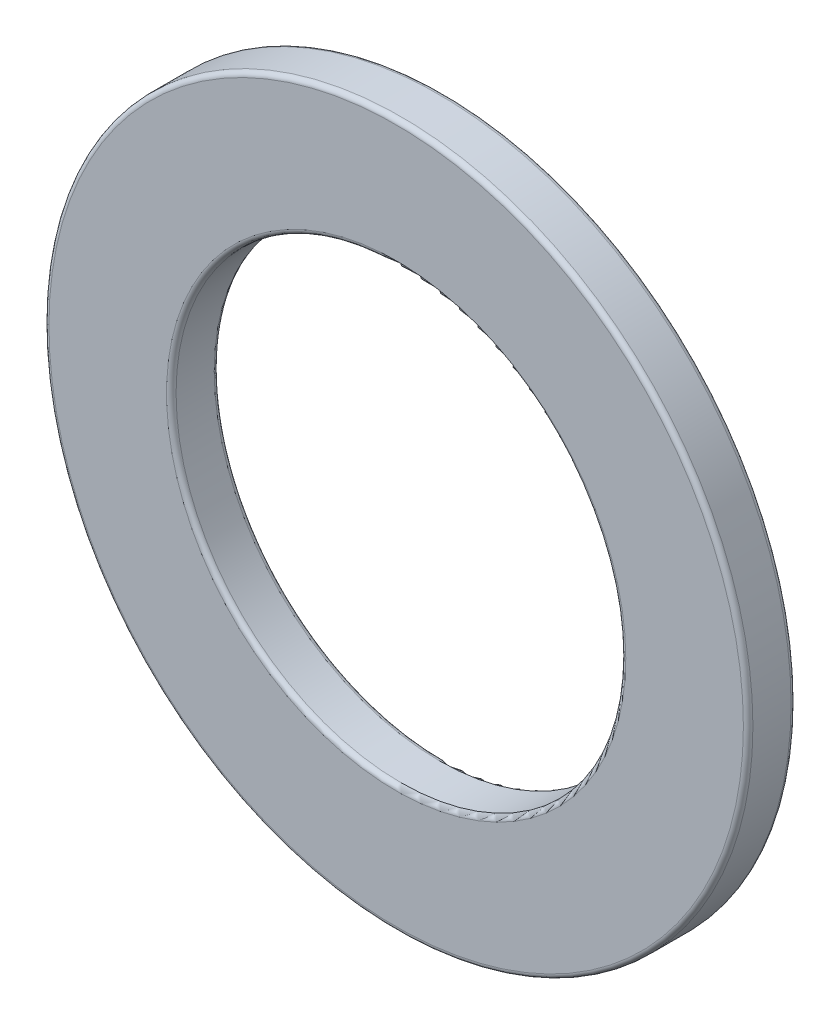
SolidWorks part; units mm, degrees
ref_plane "Front Plane" through (0, 0, 0) normal (0, 0, 1) x (1, 0, 0)
ref_plane "Top Plane" through (0, 0, 0) normal (0, 1, 0) x (1, 0, 0)
ref_plane "Right Plane" through (0, 0, 0) normal (1, 0, 0) x (0, 0, -1)
sketch "Sketch1" plane through (0, 0, 0) normal (0, 0, 1) x (1, 0, 0)
  circle A0 centre (0, 0) radius 11.075
  circle A1 centre (0, 0) radius 7.075
  dimension "D1" = 14.15
  dimension "D2" = 4
base flange "Base-Flange1" sketch "Sketch1" thickness 1.5 reverse thickness direction no parameters "D1"=1
fillet "Fillet1" radius 0.15 4 edges at (11.075, 0, 0) (11.075, 0, -1.5) (7.075, 0, 0) (7.075, 0, -1.5)
sketch "Bend-Lines1" [suppressed] plane through (0, 0, 0) normal (0, 1, 0) x (1, 0, 0)
sketch "Bounding-Box1" [suppressed] plane through (0, 0, 0) normal (0, 1, 0) x (1, 0, 0)
sheet metal parameters "Sheet-Metal1" thickness 1.5 parameters "D1"=1
flat pattern "Flat-Pattern1" [suppressed]
sketch "Bend-Lines2" plane through (0, 0, 0) normal (0, 1, 0) x (1, 0, 0)
sketch3d "Bounding-Box2" [suppressed]
  line L0 (-11.075, -11.075, 0) -> (11.075, -11.075, 0) construction
  line L1 (-11.075, 11.075, 0) -> (11.075, 11.075, 0) construction
  line L2 (-11.075, -11.075, 0) -> (-11.075, 11.075, 0) construction
  line L3 (11.075, -11.075, 0) -> (11.075, 11.075, 0) construction
